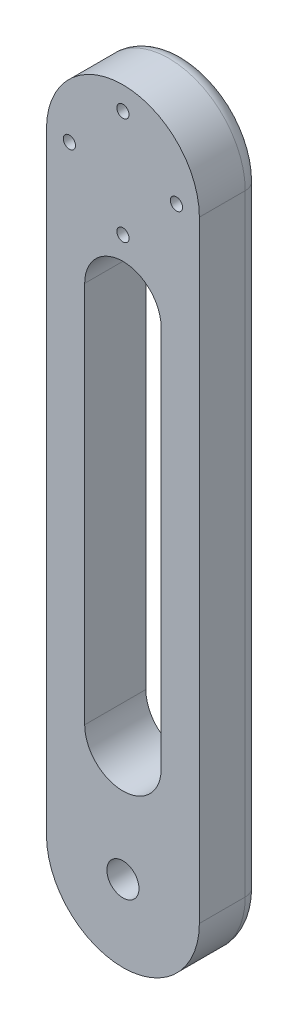
SolidWorks part; units mm, degrees
material "ABS"
ref_plane "Front Plane" through (0, 0, 0) normal (0, 0, 1) x (1, 0, 0)
ref_plane "Top Plane" through (0, 0, 0) normal (0, 1, 0) x (1, 0, 0)
ref_plane "Right Plane" through (0, 0, 0) normal (1, 0, 0) x (0, 0, -1)
sketch "Sketch1" plane through (0, 0, 0) normal (0, 0, 1) x (1, 0, 0)
  line L0 (-10, 0) -> (-10, -80)
  line L1 (-10, -80) -> (10, -80)
  line L2 (10, -80) -> (10, 0)
  circle A0 centre (0, 0) radius 10
  circle A1 centre (0, 7) radius 0.8
  circle A2 centre (7, 0) radius 0.8
  circle A3 centre (0, -7) radius 0.8
  circle A4 centre (-7, 0) radius 0.8
  circle A5 centre (0, -80) radius 10
  circle A6 centre (0, -80) radius 2.1
  point P14 (0, 0)
  dimension "D1" = 20
  dimension "D2" = 1.6
  dimension "D3" = 7
  dimension "D4" = 0
  dimension "D7" = 4.2
  dimension "D6" = 80
  dimension "D5" = 4
extrude "Boss-Extrude1" add sketch "Sketch1" along normal blind 8 contours A5 L2 A0 L0 | A0 A4 A3 A2 A1 | A6 L1 A5 | A6 L1 A5 region at (0, -40, 0) region at (0, 0, 0) region at (0, -75.6012, 0) region at (0, -84.3988, 0)
fillet "Fillet1" radius 2 4 edges at (0, -90, 0) (0, 10, 0) (-10, -40, 0) (10, -40, 0)
sketch "Sketch3" plane through (0, 0, 0) normal (0, 0, -1) x (-1, 0, 0)
  line L0 (0, -65) -> (0, -15) construction
  line L1 (-5, -65) -> (-5, -15)
  line L2 (5, -65) -> (5, -15)
  arc A0 (-5, -65) -> (5, -65) centre (0, -65) ccw
  arc A1 (5, -15) -> (-5, -15) centre (0, -15) ccw
  point P2 (0, -40)
  dimension "D1" = 5
  dimension "D2" = 50
  dimension "D3" = 40
extrude "Cut-Extrude1" cut sketch "Sketch3" against normal blind 60
